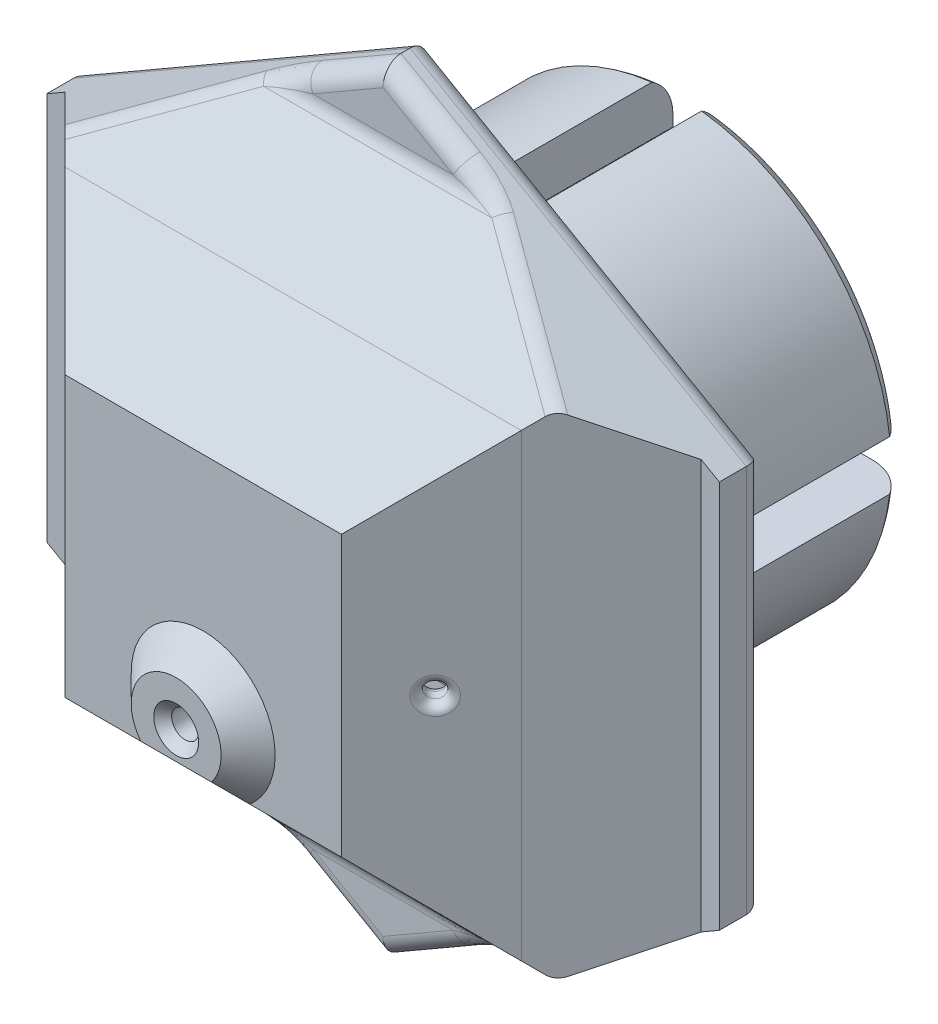
SolidWorks part; units mm, degrees
ref_plane "Plan de face" through (0, 0, 0) normal (0, 0, 1) x (1, 0, 0)
ref_plane "Plan de dessus" through (0, 0, 0) normal (0, 1, 0) x (1, 0, 0)
ref_plane "Plan de droite" through (0, 0, 0) normal (1, 0, 0) x (0, 0, -1)
sketch "Esquisse1" plane through (0, 0, 0) normal (0, 0, 1) x (1, 0, 0)
  line L0 (0, 0) -> (0, 24.6)
  line L1 (2.1, 24.6) -> (2.1, 18.2)
  line L2 (2.1, 24.6) -> (-2.1, 24.6)
  line L3 (0, 24.6) -> (0, 18.2)
  line L4 (2.1, 18.2) -> (-2.1, 18.2)
  line L5 (-2.1, 24.6) -> (-2.1, 18.2)
  line L6 (18.2, -2.1) -> (18.2, 2.1)
  line L7 (24.6, 2.1) -> (18.2, 2.1)
  line L8 (24.6, -2.1) -> (24.6, 2.1)
  line L9 (24.6, -2.1) -> (18.2, -2.1)
  line L10 (-2.1, -18.2) -> (2.1, -18.2)
  line L11 (2.1, -24.6) -> (2.1, -18.2)
  line L12 (-2.1, -24.6) -> (2.1, -24.6)
  line L13 (-2.1, -24.6) -> (-2.1, -18.2)
  line L14 (-18.2, 2.1) -> (-18.2, -2.1)
  line L15 (-24.6, -2.1) -> (-18.2, -2.1)
  line L16 (-24.6, 2.1) -> (-24.6, -2.1)
  line L17 (-24.6, 2.1) -> (-18.2, 2.1)
  circle A0 centre (0, 0) radius 24.6
  point P24 (0, 0)
  dimension "D1" = 49.2
  dimension "D2" = 4
extrude "Boss.-Extru.2" add sketch "Esquisse1" along normal blind 30
sketch "Esquisse2" plane through (0, 0, 30) normal (0, 0, 1) x (1, 0, 0)
  line L1 (-25.3712, -25.5402) -> (25.3712, -25.5402)
  line L2 (-25.3712, -25.5402) -> (-25.3712, 25.5402)
  line L3 (-25.3712, 25.5402) -> (25.3712, 25.5402)
  line L4 (25.3712, -25.5402) -> (25.3712, 25.5402)
  line L5 (-25.3712, -25.5402) -> (25.3712, 25.5402) construction
  line L6 (-25.3712, 25.5402) -> (25.3712, -25.5402) construction
  point P0 (0, 0)
extrude "Boss.-Extru.4" add sketch "Esquisse2" along normal blind 25
chamfer "Chanfrein2" distance 10 angle 45 8 edges at (0, -25.5402, 55) (-25.3712, -25.5402, 42.5) (-25.3712, 0, 55) (-25.3712, 25.5402, 42.5) (0, 25.5402, 55) (25.3712, -25.5402, 42.5) (25.3712, 0, 55) (25.3712, 25.5402, 42.5)
shell "Coque1" thickness 3
sketch "Esquisse3" plane through (35.1856, 0, 35.1856) normal (0.7071, 0, 0.7071) x (0.7071, 0, -0.7071)
  circle A0 centre (-20.6541, 0) radius 1
extrude "Enlèv. mat.-Extru.1" cut sketch "Esquisse3" against normal blind 19
sketch "Esquisse4" plane through (-35.1856, 0, 35.1856) normal (-0.7071, 0, 0.7071) x (0.7071, 0, 0.7071)
  circle A0 centre (21.2181, 0) radius 1
extrude "Enlèv. mat.-Extru.2" cut sketch "Esquisse4" against normal blind 19
fillet "Congé2" radius 1 4 edges at (21.2881, 0, 49.0831) (-19.475, 0, 50.8962) (17.7526, 0, 48.376) (-18.7679, 0, 47.3606)
sketch "Esquisse5" plane through (0, 0, 55) normal (0, 0, 1) x (1, 0, 0)
  circle A0 centre (0, -9.4386) radius 3
extrude "Boss.-Extru.5" add sketch "Esquisse5" along normal blind 3
sketch "Esquisse6" plane through (0, 0, 58) normal (0, 0, 1) x (1, 0, 0)
  circle A0 centre (0, -9.4386) radius 1.5
extrude "Enlèv. mat.-Extru.3" cut sketch "Esquisse6" against normal blind 18
chamfer "Chanfrein4" distance 5 angle 45 1 edges at (-3, -9.4386, 55)
chamfer "Chanfrein5" distance 1 angle 45 1 edges at (1.5, -9.4386, 58)
chamfer "Chanfrein6" distance 2 angle 45 1 edges at (-1.5, -9.4386, 52)
fillet "Congé6" radius 1 8 edges at (-2.1, -24.5102, 15) (2.1, -24.5102, 15) (24.5102, -2.1, 15) (24.5102, 2.1, 15) (2.1, 24.5102, 15) (-2.1, 24.5102, 15) (-24.5102, -2.1, 15) (-24.5102, 2.1, 15)
sketch "Esquisse7" plane through (0, 0, 0) normal (0, 0, -1) x (-1, 0, 0)
  line L0 (0, 18.2) -> (0, 20.5122)
  line L1 (-2.1, 18.2) -> (-2.6802, 18.2)
  line L2 (-2.1, 18.2) -> (-2.1, 24.3031)
  line L3 (-2.1, 24.3031) -> (-2.6802, 24.3031)
  line L4 (-2.6802, 18.2) -> (-2.6802, 24.3031)
  line L5 (-2.1, 18.2) -> (2.1, 18.2) construction
  line L6 (2.1, 24.3031) -> (2.6802, 24.3031)
  line L7 (2.6802, 18.2) -> (2.6802, 24.3031)
  line L8 (2.1, 18.2) -> (2.6802, 18.2)
  line L9 (2.1, 18.2) -> (2.1, 24.3031)
  line L10 (18.2, 2.1) -> (24.3031, 2.1)
  line L11 (18.2, 2.1) -> (18.2, 2.6802)
  line L12 (18.2, 2.6802) -> (24.3031, 2.6802)
  line L13 (24.3031, 2.1) -> (24.3031, 2.6802)
  line L14 (24.3031, -2.1) -> (24.3031, -2.6802)
  line L15 (18.2, -2.6802) -> (24.3031, -2.6802)
  line L16 (18.2, -2.1) -> (18.2, -2.6802)
  line L17 (18.2, -2.1) -> (24.3031, -2.1)
  line L18 (2.1, -18.2) -> (2.1, -24.3031)
  line L19 (2.1, -18.2) -> (2.6802, -18.2)
  line L20 (2.6802, -18.2) -> (2.6802, -24.3031)
  line L21 (2.1, -24.3031) -> (2.6802, -24.3031)
  line L22 (-2.1, -24.3031) -> (-2.6802, -24.3031)
  line L23 (-2.6802, -18.2) -> (-2.6802, -24.3031)
  line L24 (-2.1, -18.2) -> (-2.6802, -18.2)
  line L25 (-2.1, -18.2) -> (-2.1, -24.3031)
  line L26 (-18.2, -2.1) -> (-24.3031, -2.1)
  line L27 (-18.2, -2.1) -> (-18.2, -2.6802)
  line L28 (-18.2, -2.6802) -> (-24.3031, -2.6802)
  line L29 (-24.3031, -2.1) -> (-24.3031, -2.6802)
  line L30 (-24.3031, 2.1) -> (-24.3031, 2.6802)
  line L31 (-18.2, 2.6802) -> (-24.3031, 2.6802)
  line L32 (-18.2, 2.1) -> (-18.2, 2.6802)
  line L33 (-18.2, 2.1) -> (-24.3031, 2.1)
  arc A0 (-2.1, 23.3955) -> (-3.2314, 24.3868) centre (-3.1, 23.3955) ccw construction
  arc A1 (-2.1, 23.3955) -> (-3.2314, 24.3868) centre (-3.1, 23.3955) ccw construction
  point P47 (0, 0)
  line M26 (2.1, -18.2) -> (2.1, -23.3955)
  arc M27 (2.1, -23.3955) -> (3.2314, -24.3868) centre (3.1, -23.3955) ccw
  line M32 (18.2, 2.1) -> (23.3955, 2.1)
  arc M33 (23.3955, 2.1) -> (24.3868, 3.2314) centre (23.3955, 3.1) ccw
  arc M35 (3.2314, 24.3868) -> (2.1, 23.3955) centre (3.1, 23.3955) ccw
  line M36 (2.1, 23.3955) -> (2.1, 18.2)
  line M38 (-2.1, 18.2) -> (-2.1, 23.3955)
  arc M39 (-2.1, 23.3955) -> (-3.2314, 24.3868) centre (-3.1, 23.3955) ccw
  arc M41 (-24.3868, 3.2314) -> (-23.3955, 2.1) centre (-23.3955, 3.1) ccw
  line M42 (-23.3955, 2.1) -> (-18.2, 2.1)
  arc M47 (-3.2314, -24.3868) -> (-2.1, -23.3955) centre (-3.1, -23.3955) ccw
  line M48 (-2.1, -23.3955) -> (-2.1, -18.2)
  dimension "D1" = 4
sketch "Esquisse8" plane through (0, 0, 0) normal (0, 0, -1) x (-1, 0, 0)
  line L0 (0, 18.2) -> (0, 22.0331)
  line L1 (-2.1, 18.2) -> (-2.769, 18.2)
  line L2 (-2.1, 18.2) -> (-2.1, 24.5541)
  line L3 (-2.1, 24.5541) -> (-2.769, 24.5541)
  line L4 (-2.769, 18.2) -> (-2.769, 24.5541)
  line L5 (-2.1, 18.2) -> (2.1, 18.2) construction
  line L6 (2.1, 24.5541) -> (2.769, 24.5541)
  line L7 (2.769, 18.2) -> (2.769, 24.5541)
  line L8 (2.1, 18.2) -> (2.769, 18.2)
  line L9 (2.1, 18.2) -> (2.1, 24.5541)
  line L10 (18.2, 2.1) -> (24.5541, 2.1)
  line L11 (18.2, 2.1) -> (18.2, 2.769)
  line L12 (18.2, 2.769) -> (24.5541, 2.769)
  line L13 (24.5541, 2.1) -> (24.5541, 2.769)
  line L14 (24.5541, -2.1) -> (24.5541, -2.769)
  line L15 (18.2, -2.769) -> (24.5541, -2.769)
  line L16 (18.2, -2.1) -> (18.2, -2.769)
  line L17 (18.2, -2.1) -> (24.5541, -2.1)
  line L18 (2.1, -18.2) -> (2.1, -24.5541)
  line L19 (2.1, -18.2) -> (2.769, -18.2)
  line L20 (2.769, -18.2) -> (2.769, -24.5541)
  line L21 (2.1, -24.5541) -> (2.769, -24.5541)
  line L22 (-2.1, -24.5541) -> (-2.769, -24.5541)
  line L23 (-2.769, -18.2) -> (-2.769, -24.5541)
  line L24 (-2.1, -18.2) -> (-2.769, -18.2)
  line L25 (-2.1, -18.2) -> (-2.1, -24.5541)
  line L26 (-18.2, -2.1) -> (-24.5541, -2.1)
  line L27 (-18.2, -2.1) -> (-18.2, -2.769)
  line L28 (-18.2, -2.769) -> (-24.5541, -2.769)
  line L29 (-24.5541, -2.1) -> (-24.5541, -2.769)
  line L30 (-24.5541, 2.1) -> (-24.5541, 2.769)
  line L31 (-18.2, 2.769) -> (-24.5541, 2.769)
  line L32 (-18.2, 2.1) -> (-18.2, 2.769)
  line L33 (-18.2, 2.1) -> (-24.5541, 2.1)
  point P41 (0, 0)
  dimension "D1" = 4
extrude "Enlèv. mat.-Extru.5" cut sketch "Esquisse8" against normal up to surface (30 mm away) contours L28 L29 L26 L27 | L33 L30 L31 L32 | L25 L22 L23 L24 | L18 L21 L20 L19 | L15 L14 L17 L16 | L10 L13 L12 L11 | L4 L3 L2 L1 | L7 L6 L9 L8 up to face at (0, 0, 30)
sketch "Esquisse9" plane through (0, 0, 0) normal (0, 0, -1) x (-1, 0, 0)
  line L0 (17.3689, 2.769) -> (17.3689, -2.7513)
  line L1 (-2.769, 18.2) -> (2.7513, 18.2)
  line L2 (-2.769, 18.2) -> (-2.769, 17.3689)
  line L3 (-2.769, 17.3689) -> (2.7513, 17.3689)
  line L4 (2.7513, 18.2) -> (2.7513, 17.3689)
  line L5 (18.2, 2.769) -> (18.2, -2.7513)
  line L6 (18.2, -2.7513) -> (17.3689, -2.7513)
  line L7 (18.2, 2.769) -> (17.3689, 2.769)
  line L8 (2.769, -17.3689) -> (-2.7513, -17.3689)
  line L9 (2.769, -18.2) -> (-2.7513, -18.2)
  line L10 (-2.7513, -18.2) -> (-2.7513, -17.3689)
  line L11 (2.769, -18.2) -> (2.769, -17.3689)
  line L12 (-17.3689, -2.769) -> (-17.3689, 2.7513)
  line L13 (-18.2, -2.769) -> (-18.2, 2.7513)
  line L14 (-18.2, 2.7513) -> (-17.3689, 2.7513)
  line L15 (-18.2, -2.769) -> (-17.3689, -2.769)
  point P20 (0, 0)
  dimension "D1" = 4
extrude "Enlèv. mat.-Extru.6" cut sketch "Esquisse9" against normal up to surface (30 mm away) up to face at (0, 0, 30)
fillet "Congé7" radius 5 4 edges at (-17.3948, 17.3948, 0) (-17.3948, -17.3948, 0) (17.3948, -17.3948, 0) (17.3948, 17.3948, 0)
sketch "Esquisse10" plane through (0, 0, 30) normal (0, 0, -1) x (-1, 0, 0)
  circle A0 centre (0, 0) radius 26.5385
  circle A1 centre (0, 0) radius 23.8385
extrude "Enlèv. mat.-Extru.7" cut sketch "Esquisse10" along normal blind 63
sketch "Esquisse11" plane through (0, 0, 30) normal (0, 0, -1) x (-1, 0, 0)
  line L1 (0, 43.1729) -> (-37.3888, 21.5864)
  line L2 (-37.3888, 21.5864) -> (-37.3888, -21.5864)
  line L3 (-37.3888, -21.5864) -> (0, -43.1729)
  line L4 (0, -43.1729) -> (37.3888, -21.5864)
  line L5 (37.3888, -21.5864) -> (37.3888, 21.5864)
  line L6 (37.3888, 21.5864) -> (0, 43.1729)
  line L7 (-25.3712, 25.5402) -> (25.3712, 25.5402)
  line L8 (-25.3712, 25.5402) -> (-25.3712, -25.5402)
  line L9 (-25.3712, -25.5402) -> (25.3712, -25.5402)
  line L10 (25.3712, 25.5402) -> (25.3712, -25.5402)
  circle A0 centre (0, 0) radius 36
  circle A1 centre (0, 0) radius 37.3888 construction
  line M8 (25.3712, -25.5402) -> (25.3712, 25.5402)
  line M9 (25.3712, 25.5402) -> (-25.3712, 25.5402)
  line M10 (-25.3712, 25.5402) -> (-25.3712, -25.5402)
  line M11 (-25.3712, -25.5402) -> (25.3712, -25.5402)
extrude "Boss.-Extru.7" add sketch "Esquisse11" against normal blind 5 contours L5 L6 L1 L2 L3 L4 A0 | A0 M10 | A0 M9 | A0 M8 | A0 M11
chamfer "Chanfrein7" distance 10 angle 45 4 edges at (0, 25.5402, 35) (-25.3712, 0, 35) (25.3712, 0, 35) (0, -25.5402, 35)
fillet "Congé9" radius 2 30 edges at (-18.6944, -32.3796, 30) (18.6944, -32.3796, 30) (37.3888, 0, 30) (18.6944, 32.3796, 30) (-18.6944, 32.3796, 30) (-37.3888, 0, 30) (-18.2, -2.7601, 30) (-17.7845, -2.7513, 30) (-17.3689, 0.0089, 30) (-20.523, 2.769, 30) (-16.8564, 16.8564, 30) (-2.769, 20.9386, 30) (-2.7601, 18.2, 30) (-2.7513, 17.7845, 30) (0.0089, 17.3689, 30) (2.769, 20.523, 30) (16.8564, 16.8564, 30) (20.9386, 2.769, 30) (18.2, 2.7601, 30) (17.7845, 2.7513, 30) (17.3689, -0.0089, 30) (20.523, -2.769, 30) (16.8564, -16.8564, 30) (2.769, -20.9386, 30) (2.7601, -18.2, 30) (2.7513, -17.7845, 30) (-0.0089, -17.3689, 30) (-2.769, -20.523, 30) (-16.8564, -16.8564, 30) (-20.9386, -2.769, 30)
fillet "Congé10" radius 2 10 edges at (-20.2418, -31.4863, 39.0539) (20.2418, -31.4863, 39.0539) (20.2418, 31.4863, 39.0539) (-20.2418, 31.4863, 39.0539) (-6.6101, -39.3565, 35) (0, -35.5402, 35) (6.6101, -39.3565, 35) (6.6101, 39.3565, 35) (0, 35.5402, 35) (-6.6101, 39.3565, 35)
extrude "Enlèv. mat.-Extru.4" cut sketch "Esquisse7" against normal up to surface (30 mm away) contours L32 L31 M42 M41 | L24 L23 M48 M47 | L20 L19 M26 M27 | L12 L11 M32 M33 | L8 L7 M36 M35 | L4 L1 M38 M39 | L28 L29 L26 L27 | L15 L14 L17 L16
sketch "Esquisse12" plane through (0, 0, 30) normal (0, 0, -1) x (-1, 0, 0)
  circle A0 centre (0, 0) radius 33.9077
  circle A1 centre (0, 0) radius 25.8385
extrude "Enlèv. mat.-Extru.10" cut sketch "Esquisse12" against normal blind 2
fillet "Congé11" radius 10 1 edges at (-33.9077, 0, 32)
